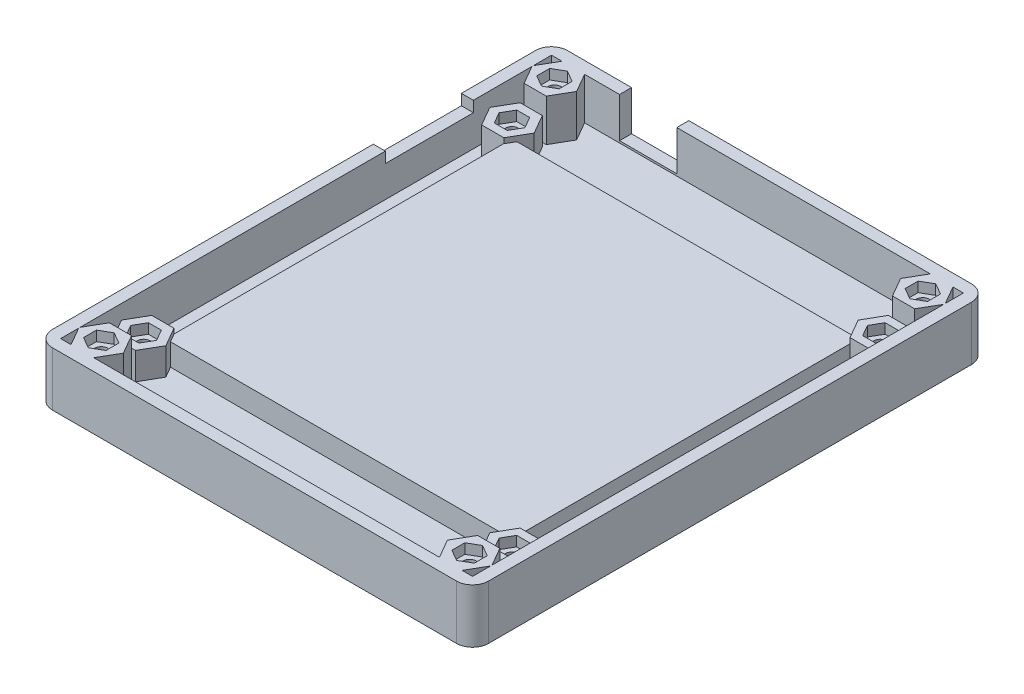
SolidWorks part; units mm, degrees
ref_plane "Přední rovina" through (0, 0, 0) normal (0, 0, 1) x (1, 0, 0)
ref_plane "Horní rovina" through (0, 0, 0) normal (0, 1, 0) x (1, 0, 0)
ref_plane "Pravá rovina" through (0, 0, 0) normal (1, 0, 0) x (0, 0, -1)
sketch "Skica1" plane through (0, 0, 0) normal (0, 1, 0) x (1, 0, 0)
  line L0 (0, 0) -> (-100, 100) construction
  line L1 (-50, 50) -> (50, 50) construction
  line L2 (-50, 50) -> (-50, -50) construction
  line L3 (-50, -50) -> (50, -50) construction
  line L4 (50, 50) -> (50, -50) construction
  line L5 (-50, 50) -> (50, -50) construction
  line L6 (-50, -50) -> (50, 50) construction
  line L7 (-47.6166, 43.2) -> (-44.3834, 43.2)
  line L8 (-44.3834, 43.2) -> (-42.7668, 46)
  line L9 (-42.7668, 46) -> (-44.3834, 48.8)
  line L10 (-44.3834, 48.8) -> (-47.6166, 48.8)
  line L11 (-47.6166, 48.8) -> (-49.2332, 46)
  line L12 (-49.2332, 46) -> (-47.6166, 43.2)
  line L13 (-48.7713, 41.2) -> (-43.2287, 41.2)
  line L14 (-43.2287, 41.2) -> (-40.4574, 46)
  line L15 (-40.4574, 46) -> (-43.2287, 50.8)
  line L16 (-43.2287, 50.8) -> (-48.7713, 50.8)
  line L17 (-48.7713, 50.8) -> (-51.5426, 46)
  line L18 (-51.5426, 46) -> (-48.7713, 41.2)
  line L19 (0, 81.3987) -> (0, -91.9033) construction
  line L20 (-46, 53.3668) -> (-43.2, 54.9834)
  line L21 (-43.2, 54.9834) -> (-43.2, 58.2166)
  line L22 (-43.2, 58.2166) -> (-46, 59.8332)
  line L23 (-46, 59.8332) -> (-48.8, 58.2166)
  line L24 (-48.8, 58.2166) -> (-48.8, 54.9834)
  line L25 (-48.8, 54.9834) -> (-46, 53.3668)
  line L26 (-48.7713, 51.8) -> (-43.2287, 51.8)
  line L27 (-43.2287, 51.8) -> (-40.4574, 56.6)
  line L28 (-40.4574, 56.6) -> (-43.2287, 61.4)
  line L29 (-43.2287, 61.4) -> (-48.7713, 61.4)
  line L30 (-48.7713, 61.4) -> (-51.5426, 56.6)
  line L31 (-51.5426, 56.6) -> (-48.7713, 51.8)
  line L36 (74.9355, -74.9355) -> (-74.9355, 74.9355) construction
  line L37 (74.9355, 74.9355) -> (-74.9355, -74.9355) construction
  line L38 (-54.4426, -64.3) -> (54.4426, -64.3)
  line L39 (-54.4426, -64.3) -> (-54.4426, 64.3)
  line L40 (-54.4426, 64.3) -> (54.4426, 64.3)
  line L41 (54.4426, -64.3) -> (54.4426, 64.3)
  line L42 (-54.4426, -64.3) -> (54.4426, 64.3) construction
  line L43 (-54.4426, 64.3) -> (54.4426, -64.3) construction
  line L44 (-106.951, 0) -> (125.2961, 0) construction
  line L45 (-46, 37.8836) -> (-46, 68.4593) construction
  line L47 (-51.4426, -61.3) -> (51.4426, -61.3)
  line L48 (-51.4426, -61.3) -> (-51.4426, 61.3)
  line L49 (-51.4426, 61.3) -> (51.4426, 61.3)
  line L50 (51.4426, -61.3) -> (51.4426, 61.3)
  line L51 (-51.4426, -61.3) -> (51.4426, 61.3) construction
  line L52 (-51.4426, 61.3) -> (51.4426, -61.3) construction
  circle A0 centre (-46, 46) radius 2.8 construction
  circle A1 centre (-46, 46) radius 4.8 construction
  circle A2 centre (-46, 56.6) radius 2.8 construction
  circle A3 centre (-46, 56.6) radius 4.8 construction
  circle A4 centre (-46, 46) radius 1.6
  circle A5 centre (-46, 56.6) radius 1.6
  point P0 (0, 0)
  point P7 (-41.8431, 43.6)
  dimension "D9" = 3
  dimension "D10" = 3
  dimension "D11" = 0.1
  dimension "D12" = 0.1
  dimension "D13" = 3.2
  dimension "D14" = 3.2
  dimension "D1" = 100
  dimension "D2" = 100
  dimension "D3" = 5.6
  dimension "D4" = 4
  dimension "D5" = 9.6
  dimension "D6" = 5.6
  dimension "D7" = 9.6
  dimension "D8" = 1
extrude "Přidat vysunutím25" add sketch "Skica1" against normal blind 3 contours L49 L48 L30 | L20 L21 L22 L23 L24 L25 | L7 L8 L9 L10 L11 L12 | L48 L47 L50 L49 | L13 L14 L15 L16 L17 L18 | L26 L27 L28 L29 L30 L31 region at (-50.5714, 0, -59.7911)
extrude "Přidat vysunutím26" add sketch "Skica1<21>" against normal blind 3 and the other way blind 10.5 contours L38 L41 L40 L39 L50 L47 L48 L18 L17 L31 L30 L49 L29 L28 | L18 L48 L17 | L31 L48 L30 | L30 L49 L28 L29 region at (-51.4759, 0, -46) region at (-51.4759, 0, -56.6) region at (-46, 0, -61.3498) region at (-52.7575, 0, 0)
sketch "Skica1<21>" plane through (0, 0, 0) normal (0, 1, 0) x (1, 0, 0) same geometry as "Skica1"
extrude "Přidat vysunutím28" add sketch "Skica1<23>" along normal blind 6.8 contours L48 L18 L13 L14 L15 L16 L17 L12 L11 L10 L9 L8 L7 | L18 L48 L17 region at (-49.9806, 0, -43.5863) region at (-51.4759, 0, -46)
sketch "Skica1<23>" plane through (0, 0, 0) normal (0, 1, 0) x (1, 0, 0) same geometry as "Skica1"
extrude "Přidat vysunutím29" add sketch "Skica1<24>" along normal blind 4.3 contours L11 L12 L7 L8 L9 L10 region at (-48.3508, 0, -44.6428)
sketch "Skica1<24>" plane through (0, 0, 0) normal (0, 1, 0) x (1, 0, 0) same geometry as "Skica1"
pattern_linear "LinPole3" count 2 spacing 92 along (1, 0, 0) count 2 spacing 92 along (0, 0, 1) of "Přidat vysunutím28", "Přidat vysunutím29"
extrude "Přidat vysunutím30" add sketch "Skica1<25>" along normal blind 10.5 contours L49 L30 L48 L31 L26 L27 L28 L25 L24 L23 L22 L21 L20 | L30 L49 L28 L29 | L31 L48 L30 region at (-51.2973, 0, -56.6) region at (-51.4759, 0, -56.6) region at (-46, 0, -61.3498)
sketch "Skica1<25>" plane through (0, 0, 0) normal (0, 1, 0) x (1, 0, 0) same geometry as "Skica1"
extrude "Přidat vysunutím31" add sketch "Skica1<26>" along normal blind 8 contours L24 L25 L20 L21 L22 L23 A5 region at (-47.3572, 0, -54.2492)
sketch "Skica1<26>" plane through (0, 0, 0) normal (0, 1, 0) x (1, 0, 0) same geometry as "Skica1"
pattern_linear "LinPole4" count 2 spacing 92 along (1, 0, 0) count 2 spacing 113.2 along (0, 0, 1) of "Přidat vysunutím31", "Přidat vysunutím30"
sketch "Skica8" plane through (0, 0, 0) normal (0, 1, 0) x (1, 0, 0)
  line L1 (-43.2691, -43.2691) -> (43.2691, -43.2691)
  line L2 (-43.2691, -43.2691) -> (-43.2691, 43.2691)
  line L3 (-43.2691, 43.2691) -> (43.2691, 43.2691)
  line L4 (43.2691, -43.2691) -> (43.2691, 43.2691)
  line L5 (-43.2691, -43.2691) -> (43.2691, 43.2691) construction
  line L6 (-43.2691, 43.2691) -> (43.2691, -43.2691) construction
  point P0 (0, 0)
  dimension "D1" = 86.5383
extrude "Přidat vysunutím32" add sketch "Skica8" along normal blind 5.5
fillet "Zaoblit4" radius 4 4 edges at (-54.4426, 3.75, 64.3) (54.4426, 3.75, 64.3) (54.4426, 3.75, -64.3) (-54.4426, 3.75, -64.3)
sketch "Skica9" plane through (-54.4426, 0, 0) normal (-1, 0, 0) x (0, 0, 1)
  line L0 (60.3, 10.5) -> (-60.3, 10.5) construction
  line L1 (-19.8, 7.8) -> (-41.8, 7.8)
  line L2 (-19.8, 7.8) -> (-19.8, 10.5)
  line L3 (-19.8, 10.5) -> (-41.8, 10.5)
  line L4 (-41.8, 7.8) -> (-41.8, 10.5)
  line L5 (-19.8, 7.8) -> (-41.8, 10.5) construction
  line L6 (-19.8, 10.5) -> (-41.8, 7.8) construction
  line L7 (-64.3, -3) -> (-64.3, 10.5) construction
  point P0 (-30.8, 9.15)
  dimension "D1" = 22
  dimension "D2" = 22.5
  dimension "D3" = 2.7
extrude "Odebrat vysunutím1" cut sketch "Skica9" against normal blind 10 contours L4 L3 L2 L1
sketch "Skica10" plane through (0, 0, -64.3) normal (0, 0, -1) x (-1, 0, 0)
  line L0 (50.4426, 10.5) -> (-50.4426, 10.5) construction
  line L1 (20.1426, 0.5) -> (34.4426, 0.5)
  line L2 (20.1426, 0.5) -> (20.1426, 10.5)
  line L3 (20.1426, 10.5) -> (34.4426, 10.5)
  line L4 (34.4426, 0.5) -> (34.4426, 10.5)
  line L5 (54.4426, 10.5) -> (54.4426, -3) construction
  dimension "D1" = 10
  dimension "D2" = 14.3
  dimension "D3" = 20
extrude "Odebrat vysunutím2" cut sketch "Skica10" against normal blind 5
